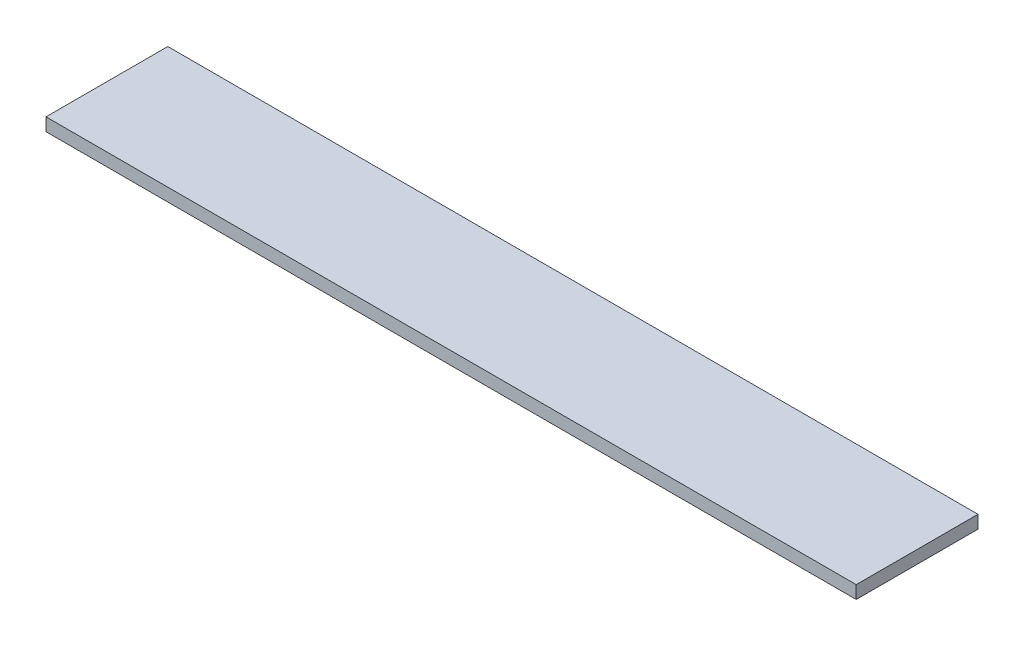
SolidWorks part; units mm, degrees
ref_plane "Front" through (0, 0, 0) normal (0, 0, 1) x (1, 0, 0)
ref_plane "Top" through (0, 0, 0) normal (0, 1, 0) x (1, 0, 0)
ref_plane "Right" through (0, 0, 0) normal (1, 0, 0) x (0, 0, -1)
sketch "Sketch1" plane through (0, 0, 0) normal (0, 1, 0) x (1, 0, 0)
  line L1 (0, 0) -> (199.58, 0)
  line L2 (0, 0) -> (0, 30)
  line L3 (0, 30) -> (199.58, 30)
  line L4 (199.58, 0) -> (199.58, 30)
  dimension "D1" = 199.58
  dimension "D2" = 30
extrude "Boss-Extrude1" add sketch "Sketch1" along normal blind 3.175
